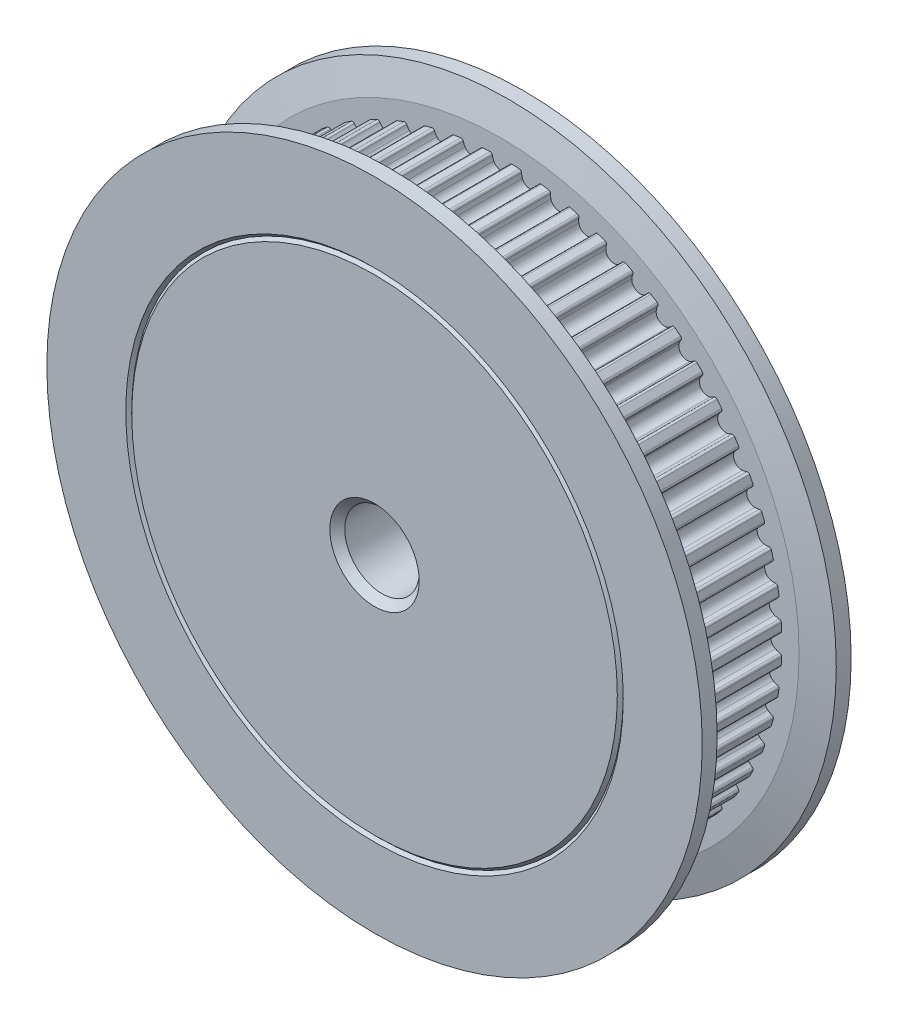
SolidWorks part; units mm, degrees
material "2219-O"
ref_plane "Спереди" through (0, 0, 0) normal (0, 0, 1) x (1, 0, 0)
ref_plane "Сверху" through (0, 0, 0) normal (0, 1, 0) x (1, 0, 0)
ref_plane "Справа" through (0, 0, 0) normal (1, 0, 0) x (0, 0, -1)
sketch "Эскиз2" plane through (0, 0, 0) normal (1, 0, 0) x (0, 0, -1)
  line L0 (-14.5523, 0) -> (18.1217, 0) construction
  line L1 (0, 0) -> (0, 16.3)
  line L2 (0, 22) -> (1.5, 22)
  line L3 (1.5, 22) -> (1.5, 18.85)
  line L4 (1.5, 18.85) -> (8.5, 18.85)
  line L5 (8.5, 18.85) -> (8.5, 22)
  line L6 (8.5, 22) -> (10, 22)
  line L7 (10, 22) -> (10, 16.7)
  line L8 (10, 16.7) -> (9.8, 16.5)
  line L9 (9.8, 16.5) -> (10, 16.3)
  line L10 (10, 16.3) -> (10, 12.5)
  line L11 (10, 12.5) -> (16, 12.5)
  line L12 (16, 12.5) -> (16, 0)
  line L13 (0, 16.7) -> (0.2, 16.5)
  line L14 (0.2, 16.5) -> (0, 16.3)
  line L15 (0, 16.7) -> (0, 22)
  line L17 (0, 2.5) -> (16, 2.5)
  dimension "D1" = 44
  dimension "D2" = 33
  dimension "D3" = 10
  dimension "D4" = 0.2
  dimension "D5" = 16
  dimension "D6" = 5
  dimension "D7" = 7
  dimension "D8" = 37.7
  dimension "D9" = 25
revolve "Повернуть1" add sketch "Эскиз2" angle 360 about L0 region at (0, 10.2506, -7.0612)
chamfer "Фаска1" distance 0.5 angle 45 4 edges at (12.5, 0, -10) (2.5, 0, 0) (12.5, 0, -16) (2.5, 0, -16)
chamfer "Фаска2" distance 2 distance2 0.5 1 edges at (22, 0, -1.5) first distance on face at (18.85, 0, -1.5)
chamfer "Фаска3" distance 0.5 distance2 2 1 edges at (22, 0, -8.5) first distance on face at (22, 0, -10)
sketch "Эскиз3" plane through (0, 0, 0) normal (0, 0, 1) x (1, 0, 0)
  line L0 (-26.2309, 18.85) -> (36.0031, 18.85) construction
  line L1 (0, 9.858) -> (0, -9.1722) construction
  line L2 (-3.2209, 18.1) -> (39.5424, 18.1) construction
  circle A0 centre (0, 0) radius 18.85 construction
  arc A1 (-0.4989, 18.4118) -> (0.4989, 18.4118) centre (0, 18.655) ccw
  arc A2 (-0.4989, 18.4118) -> (-0.6, 18.8404) centre (0.4, 18.85) cw
  arc A3 (0.4989, 18.4118) -> (0.6, 18.8404) centre (-0.4, 18.85) ccw
  arc A4 (-0.6, 18.8404) -> (0.6, 18.8404) centre (0, 0) cw
  arc A5 (1.3727, 18.8) -> (2.566, 18.6745) centre (0, 0) cw
  arc A6 (1.4284, 18.3631) -> (1.3727, 18.8) centre (2.3682, 18.7049) cw
  arc A7 (1.4284, 18.3631) -> (2.4207, 18.2588) centre (1.95, 18.5528) ccw
  arc A8 (2.4207, 18.2588) -> (2.566, 18.6745) centre (1.5726, 18.7885) ccw
  arc A9 (3.3303, 18.5535) -> (4.504, 18.304) centre (0, 0) cw
  arc A10 (3.3401, 18.1132) -> (3.3303, 18.5535) centre (4.3104, 18.3549) cw
  arc A11 (3.3401, 18.1132) -> (4.316, 17.9057) centre (3.8786, 18.2473) ccw
  arc A12 (4.316, 17.9057) -> (4.504, 18.304) centre (3.5279, 18.5212) ccw
  arc A13 (5.2514, 18.1037) -> (6.3926, 17.7329) centre (0, 0) cw
  arc A14 (5.2151, 17.6648) -> (5.2514, 18.1037) centre (6.2054, 17.8038) cw
  arc A15 (5.2151, 17.6648) -> (6.164, 17.3565) centre (5.7647, 17.742) ccw
  arc A16 (6.164, 17.3565) -> (6.3926, 17.7329) centre (5.4445, 18.051) ccw
  arc A17 (7.115, 17.4556) -> (8.2112, 16.9676) centre (0, 0) cw
  arc A18 (7.033, 17.0229) -> (7.115, 17.4556) centre (8.0324, 17.0576) cw
  arc A19 (7.033, 17.0229) -> (7.9445, 16.6171) centre (7.5877, 17.0422) ccw
  arc A20 (7.9445, 16.6171) -> (8.2112, 16.9676) centre (7.3016, 17.383) ccw
  arc A21 (8.9006, 16.6163) -> (9.9398, 16.0163) centre (0, 0) cw
  arc A22 (8.7739, 16.1945) -> (8.9006, 16.6163) centre (9.7714, 16.1246) cw
  arc A23 (8.7739, 16.1945) -> (9.6379, 15.6956) centre (9.3275, 16.1557) ccw
  arc A24 (9.6379, 15.6956) -> (9.9398, 16.0163) centre (9.0786, 16.5246) ccw
  arc A25 (10.5888, 15.5949) -> (11.5595, 14.8896) centre (0, 0) cw
  arc A26 (10.4186, 15.1887) -> (10.5888, 15.5949) centre (11.4034, 15.0149) cw
  arc A27 (10.4186, 15.1887) -> (11.2258, 14.6022) centre (10.9651, 15.0922) ccw
  arc A28 (11.2258, 14.6022) -> (11.5595, 14.8896) centre (10.7561, 15.4851) ccw
  arc A29 (12.1609, 14.4026) -> (13.0526, 13.5997) centre (0, 0) cw
  arc A30 (11.9492, 14.0164) -> (12.1609, 14.4026) centre (12.9104, 13.7406) cw
  arc A31 (11.9492, 14.0164) -> (12.6906, 13.3488) centre (12.4826, 13.8634) ccw
  arc A32 (12.6906, 13.3488) -> (13.0526, 13.5997) centre (12.3159, 14.2759) ccw
  arc A33 (13.5997, 13.0526) -> (14.4026, 12.1609) centre (0, 0) cw
  arc A34 (13.3488, 12.6906) -> (13.5997, 13.0526) centre (14.2759, 12.3159) cw
  arc A35 (13.3488, 12.6906) -> (14.0164, 11.9492) centre (13.8634, 12.4826) ccw
  arc A36 (14.0164, 11.9492) -> (14.4026, 12.1609) centre (13.7406, 12.9104) ccw
  arc A37 (14.8896, 11.5595) -> (15.5949, 10.5888) centre (0, 0) cw
  arc A38 (14.6022, 11.2258) -> (14.8896, 11.5595) centre (15.4851, 10.7561) cw
  arc A39 (14.6022, 11.2258) -> (15.1887, 10.4186) centre (15.0922, 10.9651) ccw
  arc A40 (15.1887, 10.4186) -> (15.5949, 10.5888) centre (15.0149, 11.4034) ccw
  arc A41 (16.0163, 9.9398) -> (16.6163, 8.9006) centre (0, 0) cw
  arc A42 (15.6956, 9.6379) -> (16.0163, 9.9398) centre (16.5246, 9.0786) cw
  arc A43 (15.6956, 9.6379) -> (16.1945, 8.7739) centre (16.1557, 9.3275) ccw
  arc A44 (16.1945, 8.7739) -> (16.6163, 8.9006) centre (16.1246, 9.7714) ccw
  arc A45 (16.9676, 8.2112) -> (17.4556, 7.115) centre (0, 0) cw
  arc A46 (16.6171, 7.9445) -> (16.9676, 8.2112) centre (17.383, 7.3016) cw
  arc A47 (16.6171, 7.9445) -> (17.0229, 7.033) centre (17.0422, 7.5877) ccw
  arc A48 (17.0229, 7.033) -> (17.4556, 7.115) centre (17.0576, 8.0324) ccw
  arc A49 (17.7329, 6.3926) -> (18.1037, 5.2514) centre (0, 0) cw
  arc A50 (17.3565, 6.164) -> (17.7329, 6.3926) centre (18.051, 5.4445) cw
  arc A51 (17.3565, 6.164) -> (17.6648, 5.2151) centre (17.742, 5.7647) ccw
  arc A52 (17.6648, 5.2151) -> (18.1037, 5.2514) centre (17.8038, 6.2054) ccw
  arc A53 (18.304, 4.504) -> (18.5535, 3.3303) centre (0, 0) cw
  arc A54 (17.9057, 4.316) -> (18.304, 4.504) centre (18.5212, 3.5279) cw
  arc A55 (17.9057, 4.316) -> (18.1132, 3.3401) centre (18.2473, 3.8786) ccw
  arc A56 (18.1132, 3.3401) -> (18.5535, 3.3303) centre (18.3549, 4.3104) ccw
  arc A57 (18.6745, 2.566) -> (18.8, 1.3727) centre (0, 0) cw
  arc A58 (18.2588, 2.4207) -> (18.6745, 2.566) centre (18.7885, 1.5726) cw
  arc A59 (18.2588, 2.4207) -> (18.3631, 1.4284) centre (18.5528, 1.95) ccw
  arc A60 (18.3631, 1.4284) -> (18.8, 1.3727) centre (18.7049, 2.3682) ccw
  arc A61 (18.8404, 0.6) -> (18.8404, -0.6) centre (0, 0) cw
  arc A62 (18.4118, 0.4989) -> (18.8404, 0.6) centre (18.85, -0.4) cw
  arc A63 (18.4118, 0.4989) -> (18.4118, -0.4989) centre (18.655, 0) ccw
  arc A64 (18.4118, -0.4989) -> (18.8404, -0.6) centre (18.85, 0.4) ccw
  arc A65 (18.8, -1.3727) -> (18.6745, -2.566) centre (0, 0) cw
  arc A66 (18.3631, -1.4284) -> (18.8, -1.3727) centre (18.7049, -2.3682) cw
  arc A67 (18.3631, -1.4284) -> (18.2588, -2.4207) centre (18.5528, -1.95) ccw
  arc A68 (18.2588, -2.4207) -> (18.6745, -2.566) centre (18.7885, -1.5726) ccw
  arc A69 (18.5535, -3.3303) -> (18.304, -4.504) centre (0, 0) cw
  arc A70 (18.1132, -3.3401) -> (18.5535, -3.3303) centre (18.3549, -4.3104) cw
  arc A71 (18.1132, -3.3401) -> (17.9057, -4.316) centre (18.2473, -3.8786) ccw
  arc A72 (17.9057, -4.316) -> (18.304, -4.504) centre (18.5212, -3.5279) ccw
  arc A73 (18.1037, -5.2514) -> (17.7329, -6.3926) centre (0, 0) cw
  arc A74 (17.6648, -5.2151) -> (18.1037, -5.2514) centre (17.8038, -6.2054) cw
  arc A75 (17.6648, -5.2151) -> (17.3565, -6.164) centre (17.742, -5.7647) ccw
  arc A76 (17.3565, -6.164) -> (17.7329, -6.3926) centre (18.051, -5.4445) ccw
  arc A77 (17.4556, -7.115) -> (16.9676, -8.2112) centre (0, 0) cw
  arc A78 (17.0229, -7.033) -> (17.4556, -7.115) centre (17.0576, -8.0324) cw
  arc A79 (17.0229, -7.033) -> (16.6171, -7.9445) centre (17.0422, -7.5877) ccw
  arc A80 (16.6171, -7.9445) -> (16.9676, -8.2112) centre (17.383, -7.3016) ccw
  arc A81 (16.6163, -8.9006) -> (16.0163, -9.9398) centre (0, 0) cw
  arc A82 (16.1945, -8.7739) -> (16.6163, -8.9006) centre (16.1246, -9.7714) cw
  arc A83 (16.1945, -8.7739) -> (15.6956, -9.6379) centre (16.1557, -9.3275) ccw
  arc A84 (15.6956, -9.6379) -> (16.0163, -9.9398) centre (16.5246, -9.0786) ccw
  arc A85 (15.5949, -10.5888) -> (14.8896, -11.5595) centre (0, 0) cw
  arc A86 (15.1887, -10.4186) -> (15.5949, -10.5888) centre (15.0149, -11.4034) cw
  arc A87 (15.1887, -10.4186) -> (14.6022, -11.2258) centre (15.0922, -10.9651) ccw
  arc A88 (14.6022, -11.2258) -> (14.8896, -11.5595) centre (15.4851, -10.7561) ccw
  arc A89 (14.4026, -12.1609) -> (13.5997, -13.0526) centre (0, 0) cw
  arc A90 (14.0164, -11.9492) -> (14.4026, -12.1609) centre (13.7406, -12.9104) cw
  arc A91 (14.0164, -11.9492) -> (13.3488, -12.6906) centre (13.8634, -12.4826) ccw
  arc A92 (13.3488, -12.6906) -> (13.5997, -13.0526) centre (14.2759, -12.3159) ccw
  arc A93 (13.0526, -13.5997) -> (12.1609, -14.4026) centre (0, 0) cw
  arc A94 (12.6906, -13.3488) -> (13.0526, -13.5997) centre (12.3159, -14.2759) cw
  arc A95 (12.6906, -13.3488) -> (11.9492, -14.0164) centre (12.4826, -13.8634) ccw
  arc A96 (11.9492, -14.0164) -> (12.1609, -14.4026) centre (12.9104, -13.7406) ccw
  arc A97 (11.5595, -14.8896) -> (10.5888, -15.5949) centre (0, 0) cw
  arc A98 (11.2258, -14.6022) -> (11.5595, -14.8896) centre (10.7561, -15.4851) cw
  arc A99 (11.2258, -14.6022) -> (10.4186, -15.1887) centre (10.9651, -15.0922) ccw
  arc A100 (10.4186, -15.1887) -> (10.5888, -15.5949) centre (11.4034, -15.0149) ccw
  arc A101 (9.9398, -16.0163) -> (8.9006, -16.6163) centre (0, 0) cw
  arc A102 (9.6379, -15.6956) -> (9.9398, -16.0163) centre (9.0786, -16.5246) cw
  arc A103 (9.6379, -15.6956) -> (8.7739, -16.1945) centre (9.3275, -16.1557) ccw
  arc A104 (8.7739, -16.1945) -> (8.9006, -16.6163) centre (9.7714, -16.1246) ccw
  arc A105 (8.2112, -16.9676) -> (7.115, -17.4556) centre (0, 0) cw
  arc A106 (7.9445, -16.6171) -> (8.2112, -16.9676) centre (7.3016, -17.383) cw
  arc A107 (7.9445, -16.6171) -> (7.033, -17.0229) centre (7.5877, -17.0422) ccw
  arc A108 (7.033, -17.0229) -> (7.115, -17.4556) centre (8.0324, -17.0576) ccw
  arc A109 (6.3926, -17.7329) -> (5.2514, -18.1037) centre (0, 0) cw
  arc A110 (6.164, -17.3565) -> (6.3926, -17.7329) centre (5.4445, -18.051) cw
  arc A111 (6.164, -17.3565) -> (5.2151, -17.6648) centre (5.7647, -17.742) ccw
  arc A112 (5.2151, -17.6648) -> (5.2514, -18.1037) centre (6.2054, -17.8038) ccw
  arc A113 (4.504, -18.304) -> (3.3303, -18.5535) centre (0, 0) cw
  arc A114 (4.316, -17.9057) -> (4.504, -18.304) centre (3.5279, -18.5212) cw
  arc A115 (4.316, -17.9057) -> (3.3401, -18.1132) centre (3.8786, -18.2473) ccw
  arc A116 (3.3401, -18.1132) -> (3.3303, -18.5535) centre (4.3104, -18.3549) ccw
  arc A117 (2.566, -18.6745) -> (1.3727, -18.8) centre (0, 0) cw
  arc A118 (2.4207, -18.2588) -> (2.566, -18.6745) centre (1.5726, -18.7885) cw
  arc A119 (2.4207, -18.2588) -> (1.4284, -18.3631) centre (1.95, -18.5528) ccw
  arc A120 (1.4284, -18.3631) -> (1.3727, -18.8) centre (2.3682, -18.7049) ccw
  arc A121 (0.6, -18.8404) -> (-0.6, -18.8404) centre (0, 0) cw
  arc A122 (0.4989, -18.4118) -> (0.6, -18.8404) centre (-0.4, -18.85) cw
  arc A123 (0.4989, -18.4118) -> (-0.4989, -18.4118) centre (0, -18.655) ccw
  arc A124 (-0.4989, -18.4118) -> (-0.6, -18.8404) centre (0.4, -18.85) ccw
  arc A125 (-1.3727, -18.8) -> (-2.566, -18.6745) centre (0, 0) cw
  arc A126 (-1.4284, -18.3631) -> (-1.3727, -18.8) centre (-2.3682, -18.7049) cw
  arc A127 (-1.4284, -18.3631) -> (-2.4207, -18.2588) centre (-1.95, -18.5528) ccw
  arc A128 (-2.4207, -18.2588) -> (-2.566, -18.6745) centre (-1.5726, -18.7885) ccw
  arc A129 (-3.3303, -18.5535) -> (-4.504, -18.304) centre (0, 0) cw
  arc A130 (-3.3401, -18.1132) -> (-3.3303, -18.5535) centre (-4.3104, -18.3549) cw
  arc A131 (-3.3401, -18.1132) -> (-4.316, -17.9057) centre (-3.8786, -18.2473) ccw
  arc A132 (-4.316, -17.9057) -> (-4.504, -18.304) centre (-3.5279, -18.5212) ccw
  arc A133 (-5.2514, -18.1037) -> (-6.3926, -17.7329) centre (0, 0) cw
  arc A134 (-5.2151, -17.6648) -> (-5.2514, -18.1037) centre (-6.2054, -17.8038) cw
  arc A135 (-5.2151, -17.6648) -> (-6.164, -17.3565) centre (-5.7647, -17.742) ccw
  arc A136 (-6.164, -17.3565) -> (-6.3926, -17.7329) centre (-5.4445, -18.051) ccw
  arc A137 (-7.115, -17.4556) -> (-8.2112, -16.9676) centre (0, 0) cw
  arc A138 (-7.033, -17.0229) -> (-7.115, -17.4556) centre (-8.0324, -17.0576) cw
  arc A139 (-7.033, -17.0229) -> (-7.9445, -16.6171) centre (-7.5877, -17.0422) ccw
  arc A140 (-7.9445, -16.6171) -> (-8.2112, -16.9676) centre (-7.3016, -17.383) ccw
  arc A141 (-8.9006, -16.6163) -> (-9.9398, -16.0163) centre (0, 0) cw
  arc A142 (-8.7739, -16.1945) -> (-8.9006, -16.6163) centre (-9.7714, -16.1246) cw
  arc A143 (-8.7739, -16.1945) -> (-9.6379, -15.6956) centre (-9.3275, -16.1557) ccw
  arc A144 (-9.6379, -15.6956) -> (-9.9398, -16.0163) centre (-9.0786, -16.5246) ccw
  arc A145 (-10.5888, -15.5949) -> (-11.5595, -14.8896) centre (0, 0) cw
  arc A146 (-10.4186, -15.1887) -> (-10.5888, -15.5949) centre (-11.4034, -15.0149) cw
  arc A147 (-10.4186, -15.1887) -> (-11.2258, -14.6022) centre (-10.9651, -15.0922) ccw
  arc A148 (-11.2258, -14.6022) -> (-11.5595, -14.8896) centre (-10.7561, -15.4851) ccw
  arc A149 (-12.1609, -14.4026) -> (-13.0526, -13.5997) centre (0, 0) cw
  arc A150 (-11.9492, -14.0164) -> (-12.1609, -14.4026) centre (-12.9104, -13.7406) cw
  arc A151 (-11.9492, -14.0164) -> (-12.6906, -13.3488) centre (-12.4826, -13.8634) ccw
  arc A152 (-12.6906, -13.3488) -> (-13.0526, -13.5997) centre (-12.3159, -14.2759) ccw
  arc A153 (-13.5997, -13.0526) -> (-14.4026, -12.1609) centre (0, 0) cw
  arc A154 (-13.3488, -12.6906) -> (-13.5997, -13.0526) centre (-14.2759, -12.3159) cw
  arc A155 (-13.3488, -12.6906) -> (-14.0164, -11.9492) centre (-13.8634, -12.4826) ccw
  arc A156 (-14.0164, -11.9492) -> (-14.4026, -12.1609) centre (-13.7406, -12.9104) ccw
  arc A157 (-14.8896, -11.5595) -> (-15.5949, -10.5888) centre (0, 0) cw
  arc A158 (-14.6022, -11.2258) -> (-14.8896, -11.5595) centre (-15.4851, -10.7561) cw
  arc A159 (-14.6022, -11.2258) -> (-15.1887, -10.4186) centre (-15.0922, -10.9651) ccw
  arc A160 (-15.1887, -10.4186) -> (-15.5949, -10.5888) centre (-15.0149, -11.4034) ccw
  arc A161 (-16.0163, -9.9398) -> (-16.6163, -8.9006) centre (0, 0) cw
  arc A162 (-15.6956, -9.6379) -> (-16.0163, -9.9398) centre (-16.5246, -9.0786) cw
  arc A163 (-15.6956, -9.6379) -> (-16.1945, -8.7739) centre (-16.1557, -9.3275) ccw
  arc A164 (-16.1945, -8.7739) -> (-16.6163, -8.9006) centre (-16.1246, -9.7714) ccw
  arc A165 (-16.9676, -8.2112) -> (-17.4556, -7.115) centre (0, 0) cw
  arc A166 (-16.6171, -7.9445) -> (-16.9676, -8.2112) centre (-17.383, -7.3016) cw
  arc A167 (-16.6171, -7.9445) -> (-17.0229, -7.033) centre (-17.0422, -7.5877) ccw
  arc A168 (-17.0229, -7.033) -> (-17.4556, -7.115) centre (-17.0576, -8.0324) ccw
  arc A169 (-17.7329, -6.3926) -> (-18.1037, -5.2514) centre (0, 0) cw
  arc A170 (-17.3565, -6.164) -> (-17.7329, -6.3926) centre (-18.051, -5.4445) cw
  arc A171 (-17.3565, -6.164) -> (-17.6648, -5.2151) centre (-17.742, -5.7647) ccw
  arc A172 (-17.6648, -5.2151) -> (-18.1037, -5.2514) centre (-17.8038, -6.2054) ccw
  arc A173 (-18.304, -4.504) -> (-18.5535, -3.3303) centre (0, 0) cw
  arc A174 (-17.9057, -4.316) -> (-18.304, -4.504) centre (-18.5212, -3.5279) cw
  arc A175 (-17.9057, -4.316) -> (-18.1132, -3.3401) centre (-18.2473, -3.8786) ccw
  arc A176 (-18.1132, -3.3401) -> (-18.5535, -3.3303) centre (-18.3549, -4.3104) ccw
  arc A177 (-18.6745, -2.566) -> (-18.8, -1.3727) centre (0, 0) cw
  arc A178 (-18.2588, -2.4207) -> (-18.6745, -2.566) centre (-18.7885, -1.5726) cw
  arc A179 (-18.2588, -2.4207) -> (-18.3631, -1.4284) centre (-18.5528, -1.95) ccw
  arc A180 (-18.3631, -1.4284) -> (-18.8, -1.3727) centre (-18.7049, -2.3682) ccw
  arc A181 (-18.8404, -0.6) -> (-18.8404, 0.6) centre (0, 0) cw
  arc A182 (-18.4118, -0.4989) -> (-18.8404, -0.6) centre (-18.85, 0.4) cw
  arc A183 (-18.4118, -0.4989) -> (-18.4118, 0.4989) centre (-18.655, 0) ccw
  arc A184 (-18.4118, 0.4989) -> (-18.8404, 0.6) centre (-18.85, -0.4) ccw
  arc A185 (-18.8, 1.3727) -> (-18.6745, 2.566) centre (0, 0) cw
  arc A186 (-18.3631, 1.4284) -> (-18.8, 1.3727) centre (-18.7049, 2.3682) cw
  arc A187 (-18.3631, 1.4284) -> (-18.2588, 2.4207) centre (-18.5528, 1.95) ccw
  arc A188 (-18.2588, 2.4207) -> (-18.6745, 2.566) centre (-18.7885, 1.5726) ccw
  arc A189 (-18.5535, 3.3303) -> (-18.304, 4.504) centre (0, 0) cw
  arc A190 (-18.1132, 3.3401) -> (-18.5535, 3.3303) centre (-18.3549, 4.3104) cw
  arc A191 (-18.1132, 3.3401) -> (-17.9057, 4.316) centre (-18.2473, 3.8786) ccw
  arc A192 (-17.9057, 4.316) -> (-18.304, 4.504) centre (-18.5212, 3.5279) ccw
  arc A193 (-18.1037, 5.2514) -> (-17.7329, 6.3926) centre (0, 0) cw
  arc A194 (-17.6648, 5.2151) -> (-18.1037, 5.2514) centre (-17.8038, 6.2054) cw
  arc A195 (-17.6648, 5.2151) -> (-17.3565, 6.164) centre (-17.742, 5.7647) ccw
  arc A196 (-17.3565, 6.164) -> (-17.7329, 6.3926) centre (-18.051, 5.4445) ccw
  arc A197 (-17.4556, 7.115) -> (-16.9676, 8.2112) centre (0, 0) cw
  arc A198 (-17.0229, 7.033) -> (-17.4556, 7.115) centre (-17.0576, 8.0324) cw
  arc A199 (-17.0229, 7.033) -> (-16.6171, 7.9445) centre (-17.0422, 7.5877) ccw
  arc A200 (-16.6171, 7.9445) -> (-16.9676, 8.2112) centre (-17.383, 7.3016) ccw
  arc A201 (-16.6163, 8.9006) -> (-16.0163, 9.9398) centre (0, 0) cw
  arc A202 (-16.1945, 8.7739) -> (-16.6163, 8.9006) centre (-16.1246, 9.7714) cw
  arc A203 (-16.1945, 8.7739) -> (-15.6956, 9.6379) centre (-16.1557, 9.3275) ccw
  arc A204 (-15.6956, 9.6379) -> (-16.0163, 9.9398) centre (-16.5246, 9.0786) ccw
  arc A205 (-15.5949, 10.5888) -> (-14.8896, 11.5595) centre (0, 0) cw
  arc A206 (-15.1887, 10.4186) -> (-15.5949, 10.5888) centre (-15.0149, 11.4034) cw
  arc A207 (-15.1887, 10.4186) -> (-14.6022, 11.2258) centre (-15.0922, 10.9651) ccw
  arc A208 (-14.6022, 11.2258) -> (-14.8896, 11.5595) centre (-15.4851, 10.7561) ccw
  arc A209 (-14.4026, 12.1609) -> (-13.5997, 13.0526) centre (0, 0) cw
  arc A210 (-14.0164, 11.9492) -> (-14.4026, 12.1609) centre (-13.7406, 12.9104) cw
  arc A211 (-14.0164, 11.9492) -> (-13.3488, 12.6906) centre (-13.8634, 12.4826) ccw
  arc A212 (-13.3488, 12.6906) -> (-13.5997, 13.0526) centre (-14.2759, 12.3159) ccw
  arc A213 (-13.0526, 13.5997) -> (-12.1609, 14.4026) centre (0, 0) cw
  arc A214 (-12.6906, 13.3488) -> (-13.0526, 13.5997) centre (-12.3159, 14.2759) cw
  arc A215 (-12.6906, 13.3488) -> (-11.9492, 14.0164) centre (-12.4826, 13.8634) ccw
  arc A216 (-11.9492, 14.0164) -> (-12.1609, 14.4026) centre (-12.9104, 13.7406) ccw
  arc A217 (-11.5595, 14.8896) -> (-10.5888, 15.5949) centre (0, 0) cw
  arc A218 (-11.2258, 14.6022) -> (-11.5595, 14.8896) centre (-10.7561, 15.4851) cw
  arc A219 (-11.2258, 14.6022) -> (-10.4186, 15.1887) centre (-10.9651, 15.0922) ccw
  arc A220 (-10.4186, 15.1887) -> (-10.5888, 15.5949) centre (-11.4034, 15.0149) ccw
  arc A221 (-9.9398, 16.0163) -> (-8.9006, 16.6163) centre (0, 0) cw
  arc A222 (-9.6379, 15.6956) -> (-9.9398, 16.0163) centre (-9.0786, 16.5246) cw
  arc A223 (-9.6379, 15.6956) -> (-8.7739, 16.1945) centre (-9.3275, 16.1557) ccw
  arc A224 (-8.7739, 16.1945) -> (-8.9006, 16.6163) centre (-9.7714, 16.1246) ccw
  arc A225 (-8.2112, 16.9676) -> (-7.115, 17.4556) centre (0, 0) cw
  arc A226 (-7.9445, 16.6171) -> (-8.2112, 16.9676) centre (-7.3016, 17.383) cw
  arc A227 (-7.9445, 16.6171) -> (-7.033, 17.0229) centre (-7.5877, 17.0422) ccw
  arc A228 (-7.033, 17.0229) -> (-7.115, 17.4556) centre (-8.0324, 17.0576) ccw
  arc A229 (-6.3926, 17.7329) -> (-5.2514, 18.1037) centre (0, 0) cw
  arc A230 (-6.164, 17.3565) -> (-6.3926, 17.7329) centre (-5.4445, 18.051) cw
  arc A231 (-6.164, 17.3565) -> (-5.2151, 17.6648) centre (-5.7647, 17.742) ccw
  arc A232 (-5.2151, 17.6648) -> (-5.2514, 18.1037) centre (-6.2054, 17.8038) ccw
  arc A233 (-4.504, 18.304) -> (-3.3303, 18.5535) centre (0, 0) cw
  arc A234 (-4.316, 17.9057) -> (-4.504, 18.304) centre (-3.5279, 18.5212) cw
  arc A235 (-4.316, 17.9057) -> (-3.3401, 18.1132) centre (-3.8786, 18.2473) ccw
  arc A236 (-3.3401, 18.1132) -> (-3.3303, 18.5535) centre (-4.3104, 18.3549) ccw
  arc A237 (-2.566, 18.6745) -> (-1.3727, 18.8) centre (0, 0) cw
  arc A238 (-2.4207, 18.2588) -> (-2.566, 18.6745) centre (-1.5726, 18.7885) cw
  arc A239 (-2.4207, 18.2588) -> (-1.4284, 18.3631) centre (-1.95, 18.5528) ccw
  arc A240 (-1.4284, 18.3631) -> (-1.3727, 18.8) centre (-2.3682, 18.7049) ccw
  point P492 (0, 0)
  dimension "D1" = 37.7
  dimension "D2" = 0.555
  dimension "D4" = 1
  dimension "D3" = 0.75
  dimension "D5" = 60
extrude "Вырез-Вытянуть4" cut sketch "Эскиз3" against normal up to surface (8.5 mm away) from offset 1.5 up to face at (20, 0, -8.5) offset against normal yes
fillet "Скругление1" radius 0.15 120 edges at (18.8404, 0.6, -5) (18.8, 1.3727, -5) (18.6745, 2.566, -5) (18.5535, 3.3303, -5) (18.304, 4.504, -5) (18.1037, 5.2514, -5) (17.7329, 6.3926, -5) (17.4556, 7.115, -5) (16.9676, 8.2112, -5) (16.6163, 8.9006, -5) (16.0163, 9.9398, -5) (15.5949, 10.5888, -5) (14.8896, 11.5595, -5) (14.4026, 12.1609, -5) (13.5997, 13.0526, -5) (13.0526, 13.5997, -5) (12.1609, 14.4026, -5) (11.5595, 14.8896, -5) (10.5888, 15.5949, -5) (9.9398, 16.0163, -5) (8.9006, 16.6163, -5) (8.2112, 16.9676, -5) (7.115, 17.4556, -5) (6.3926, 17.7329, -5) (5.2514, 18.1037, -5) (4.504, 18.304, -5) (3.3303, 18.5535, -5) (2.566, 18.6745, -5) (1.3727, 18.8, -5) (0.6, 18.8404, -5) (-0.6, 18.8404, -5) (-1.3727, 18.8, -5) (-2.566, 18.6745, -5) (-3.3303, 18.5535, -5) (-4.504, 18.304, -5) (-5.2514, 18.1037, -5) (-6.3926, 17.7329, -5) (-7.115, 17.4556, -5) (-8.2112, 16.9676, -5) (-8.9006, 16.6163, -5) (-9.9398, 16.0163, -5) (-10.5888, 15.5949, -5) (-11.5595, 14.8896, -5) (-12.1609, 14.4026, -5) (-13.0526, 13.5997, -5) (-13.5997, 13.0526, -5) (-14.4026, 12.1609, -5) (-14.8896, 11.5595, -5) (-15.5949, 10.5888, -5) (-16.0163, 9.9398, -5) (-16.6163, 8.9006, -5) (-16.9676, 8.2112, -5) (-17.4556, 7.115, -5) (-17.7329, 6.3926, -5) (-18.1037, 5.2514, -5) (-18.304, 4.504, -5) (-18.5535, 3.3303, -5) (-18.6745, 2.566, -5) (-18.8, 1.3727, -5) (-18.8404, 0.6, -5) (-18.8404, -0.6, -5) (-18.8, -1.3727, -5) (-18.6745, -2.566, -5) (-18.5535, -3.3303, -5) (-18.304, -4.504, -5) (-18.1037, -5.2514, -5) (-17.7329, -6.3926, -5) (-17.4556, -7.115, -5) (-16.9676, -8.2112, -5) (-16.6163, -8.9006, -5) (-16.0163, -9.9398, -5) (-15.5949, -10.5888, -5) (-14.8896, -11.5595, -5) (-14.4026, -12.1609, -5) (-13.5997, -13.0526, -5) (-13.0526, -13.5997, -5) (-12.1609, -14.4026, -5) (-11.5595, -14.8896, -5) (-10.5888, -15.5949, -5) (-9.9398, -16.0163, -5) (-8.9006, -16.6163, -5) (-8.2112, -16.9676, -5) (-7.115, -17.4556, -5) (-6.3926, -17.7329, -5) (-5.2514, -18.1037, -5) (-4.504, -18.304, -5) (-3.3303, -18.5535, -5) (-2.566, -18.6745, -5) (-1.3727, -18.8, -5) (-0.6, -18.8404, -5) (0.6, -18.8404, -5) (1.3727, -18.8, -5) (2.566, -18.6745, -5) (3.3303, -18.5535, -5) (4.504, -18.304, -5) (5.2514, -18.1037, -5) (6.3926, -17.7329, -5) (7.115, -17.4556, -5) (8.2112, -16.9676, -5) (8.9006, -16.6163, -5) (9.9398, -16.0163, -5) (10.5888, -15.5949, -5) (11.5595, -14.8896, -5) (12.1609, -14.4026, -5) (13.0526, -13.5997, -5) (13.5997, -13.0526, -5) (14.4026, -12.1609, -5) (14.8896, -11.5595, -5) (15.5949, -10.5888, -5) (16.0163, -9.9398, -5) (16.6163, -8.9006, -5) (16.9676, -8.2112, -5) (17.4556, -7.115, -5) (17.7329, -6.3926, -5) (18.1037, -5.2514, -5) (18.304, -4.504, -5) (18.5535, -3.3303, -5) (18.6745, -2.566, -5) (18.8, -1.3727, -5) (18.8404, -0.6, -5)
